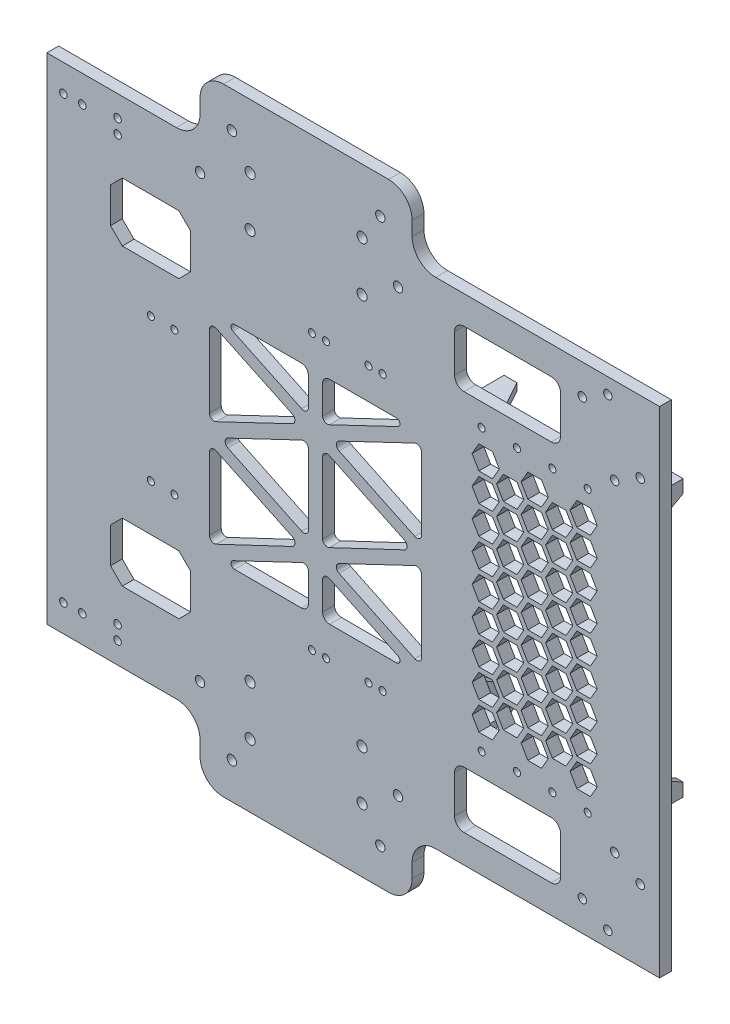
SolidWorks part; units mm, degrees
ref_plane "前视基准面" through (0, 0, 0) normal (0, 0, 1) x (1, 0, 0)
ref_plane "上视基准面" through (0, 0, 0) normal (0, 1, 0) x (1, 0, 0)
ref_plane "右视基准面" through (0, 0, 0) normal (1, 0, 0) x (0, 0, -1)
sketch "草图1" plane through (0, 0, 0) normal (0, 0, 1) x (1, 0, 0)
  line L2 (-130, 105) -> (-130, -105)
  line L3 (-130, -105) -> (-75, -105)
  line L4 (130, 95) -> (130, -95)
  line L5 (126.7518, 102.3765) -> (130, 105) construction
  line L9 (-65, -115) -> (-65, -121)
  line L10 (-55, -131) -> (15, -131)
  line L11 (25, -121) -> (25, -115)
  line L13 (35, -105) -> (120, -105)
  line L14 (126.7518, -102.3765) -> (130, -105) construction
  line L16 (-130, 0) -> (130, 0) construction
  line L17 (35, 105) -> (120, 105)
  line L18 (25, 121) -> (25, 115)
  line L19 (-55, 131) -> (15, 131)
  line L20 (-65, 115) -> (-65, 121)
  line L21 (-130, 105) -> (-75, 105)
  arc A3 (120, -105) -> (130, -95) centre (120, -95) ccw
  arc A8 (-65, -115) -> (-75, -105) centre (-75, -115) ccw
  arc A9 (25, -115) -> (35, -105) centre (35, -115) cw
  arc A10 (-55, -131) -> (-65, -121) centre (-55, -121) cw
  arc A11 (15, -131) -> (25, -121) centre (15, -121) ccw
  arc A12 (15, 131) -> (25, 121) centre (15, 121) cw
  arc A13 (-55, 131) -> (-65, 121) centre (-55, 121) ccw
  arc A14 (25, 115) -> (35, 105) centre (35, 115) ccw
  arc A15 (-65, 115) -> (-75, 105) centre (-75, 115) cw
  arc A16 (120, 105) -> (130, 95) centre (120, 95) cw
  point P0 (0, 0)
  point P7 (0, 0)
  point P10 (0, 0)
  point P11 (-130, -104.6435)
  point P34 (0, 0)
  point P36 (0, 0)
  point P40 (25, -105)
  point P45 (25, 105)
  point P47 (0, 0)
  dimension "D3" = 65
  dimension "D4" = 10
  dimension "D5" = 105
  dimension "D7" = 10
  dimension "D8" = 10
  dimension "D10" = 10
  dimension "D12" = 10
  dimension "D13" = 105
  dimension "D18" = 90
  dimension "D19" = 6
extrude "凸台-拉伸1" add sketch "草图1" along normal blind 5
sketch "草图4" plane through (0, 0, 0) normal (0, 0, -1) x (-1, 0, 0)
  line L0 (-39, -47.5) -> (-39, -58.5)
  line L1 (-39, -58.5) -> (-50, -58.5)
  line L2 (-50, -58.5) -> (-50, -55.5)
  line L3 (-50, -55.5) -> (-42, -55.5)
  line L4 (-42, -55.5) -> (-42, -47.5)
  line L5 (-42, -47.5) -> (-39, -47.5)
  line L6 (-130, 0) -> (-25.5592, 0) construction
  line L7 (-130, -95) -> (-130, 95) construction
  line L10 (-130, -95) -> (-130, 95) construction
  dimension "D1" = 11
  dimension "D2" = 11
  dimension "D3" = 3
  dimension "D4" = 3
  dimension "D5" = 80
  dimension "D7" = 55.5
extrude "凸台-拉伸2" add sketch "草图4" along normal blind 20
sketch "草图5" plane through (0, -58.5, 0) normal (0, -1, 0) x (1, 0, 0)
  line L0 (50, -10) -> (44.5, -20)
  line L1 (50, -20) -> (50, 0) construction
  line L2 (50, -20) -> (39, -20) construction
  line L3 (44.5, -20) -> (50, -20)
  line L4 (50, -20) -> (50, -10)
  dimension "D1" = 10
  dimension "D2" = 5.5
extrude "切除-拉伸3" cut sketch "草图5" against normal blind 10
sketch "草图6" plane through (39, 0, 0) normal (-1, 0, 0) x (0, 0, 1)
  line L0 (-20, -53) -> (-10, -47.5)
  line L1 (-20, -58.5) -> (-20, -47.5) construction
  line L2 (-20, -47.5) -> (0, -47.5) construction
  line L3 (-10, -47.5) -> (-20, -47.5)
  line L4 (-20, -47.5) -> (-20, -53)
  dimension "D1" = 10
  dimension "D2" = 5.5
extrude "切除-拉伸4" cut sketch "草图6" against normal blind 10
ref_plane "基准面2" through (77, 0, 0) normal (1, 0, 0) x (0, 0, -1)
mirror "镜向1" about plane through (77, 0, 0) normal (1, 0, 0) of "凸台-拉伸2", "切除-拉伸4", "切除-拉伸3"
mirror "镜向2" about plane through (0, 0, 0) normal (0, 1, 0) of "镜向1"
sketch "草图7" plane through (0, 0, 0) normal (0, 0, -1) x (-1, 0, 0)
  line L4 (-112, -55.5) -> (-104, -55.5) construction
  line L5 (-112, 47.5) -> (-112, 55.5) construction
  line L6 (-112, 55.5) -> (-104, 55.5) construction
  line L7 (-92.013, 36) -> (-94.8997, 41)
  line L8 (-94.8997, 41) -> (-100.6732, 41)
  line L9 (-100.6732, 41) -> (-103.56, 36)
  line L10 (-103.56, 36) -> (-100.6732, 31)
  line L11 (-100.6732, 31) -> (-94.8997, 31)
  line L12 (-94.8997, 31) -> (-92.013, 36)
  line L13 (-77.0019, 36) -> (-97.7865, 36) construction
  line L14 (-74.1151, 31) -> (-71.2284, 36)
  line L15 (-71.2284, 36) -> (-74.1151, 41)
  line L16 (-74.1151, 41) -> (-79.8886, 41)
  line L17 (-79.8886, 41) -> (-82.7754, 36)
  line L18 (-82.7754, 36) -> (-79.8886, 31)
  line L19 (-79.8886, 31) -> (-74.1151, 31)
  line L20 (-92.013, 24) -> (-94.8997, 29)
  line L21 (-93.1677, 30) -> (-90.2809, 25)
  line L22 (-90.2809, 25) -> (-84.5074, 25)
  line L23 (-84.5074, 25) -> (-81.6207, 30)
  line L24 (-81.6207, 30) -> (-84.5074, 35)
  line L25 (-84.5074, 35) -> (-90.2809, 35)
  line L26 (-90.2809, 35) -> (-93.1677, 30)
  line L27 (-84.5074, 37) -> (-81.6207, 42)
  line L28 (-81.6207, 42) -> (-84.5074, 47)
  line L29 (-84.5074, 47) -> (-90.2809, 47)
  line L30 (-90.2809, 47) -> (-93.1677, 42)
  line L31 (-93.1677, 42) -> (-90.2809, 37)
  line L32 (-90.2809, 37) -> (-84.5074, 37)
  line L33 (-79.8886, 43) -> (-74.1151, 43)
  line L34 (-74.1151, 43) -> (-71.2284, 48)
  line L35 (-71.2284, 48) -> (-74.1151, 53)
  line L36 (-74.1151, 53) -> (-79.8886, 53)
  line L37 (-79.8886, 53) -> (-82.7754, 48)
  line L38 (-82.7754, 48) -> (-79.8886, 43)
  line L39 (-94.8997, 43) -> (-92.013, 48)
  line L40 (-92.013, 48) -> (-94.8997, 53)
  line L41 (-94.8997, 53) -> (-100.6732, 53)
  line L42 (-100.6732, 53) -> (-103.56, 48)
  line L43 (-103.56, 48) -> (-100.6732, 43)
  line L44 (-100.6732, 43) -> (-94.8997, 43)
  line L45 (-72.3831, 42) -> (-69.4963, 37)
  line L46 (-69.4963, 37) -> (-63.7228, 37)
  line L47 (-63.7228, 37) -> (-60.8361, 42)
  line L48 (-60.8361, 42) -> (-63.7228, 47)
  line L49 (-63.7228, 47) -> (-69.4963, 47)
  line L50 (-69.4963, 47) -> (-72.3831, 42)
  line L51 (-94.8997, 29) -> (-100.6732, 29)
  line L52 (-100.6732, 29) -> (-103.56, 24)
  line L53 (-103.56, 24) -> (-100.6732, 19)
  line L54 (-100.6732, 19) -> (-94.8997, 19)
  line L55 (-94.8997, 19) -> (-92.013, 24)
  line L56 (-93.1677, 18) -> (-90.2809, 13)
  line L57 (-90.2809, 13) -> (-84.5074, 13)
  line L58 (-84.5074, 13) -> (-81.6207, 18)
  line L59 (-81.6207, 18) -> (-84.5074, 23)
  line L60 (-84.5074, 23) -> (-90.2809, 23)
  line L61 (-90.2809, 23) -> (-93.1677, 18)
  line L62 (-74.1151, 19) -> (-71.2284, 24)
  line L63 (-71.2284, 24) -> (-74.1151, 29)
  line L64 (-74.1151, 29) -> (-79.8886, 29)
  line L65 (-79.8886, 29) -> (-82.7754, 24)
  line L66 (-82.7754, 24) -> (-79.8886, 19)
  line L67 (-79.8886, 19) -> (-74.1151, 19)
  line L68 (-72.3831, 30) -> (-69.4963, 25)
  line L69 (-69.4963, 25) -> (-63.7228, 25)
  line L70 (-63.7228, 25) -> (-60.8361, 30)
  line L71 (-60.8361, 30) -> (-63.7228, 35)
  line L72 (-63.7228, 35) -> (-69.4963, 35)
  line L73 (-69.4963, 35) -> (-72.3831, 30)
  line L74 (-92.013, 12) -> (-94.8997, 17)
  line L75 (-94.8997, 17) -> (-100.6732, 17)
  line L76 (-100.6732, 17) -> (-103.56, 12)
  line L77 (-103.56, 12) -> (-100.6732, 7)
  line L78 (-100.6732, 7) -> (-94.8997, 7)
  line L79 (-94.8997, 7) -> (-92.013, 12)
  line L80 (-93.1677, 6) -> (-90.2809, 1)
  line L81 (-90.2809, 1) -> (-84.5074, 1)
  line L82 (-84.5074, 1) -> (-81.6207, 6)
  line L83 (-81.6207, 6) -> (-84.5074, 11)
  line L84 (-84.5074, 11) -> (-90.2809, 11)
  line L85 (-90.2809, 11) -> (-93.1677, 6)
  line L86 (-74.1151, 7) -> (-71.2284, 12)
  line L87 (-71.2284, 12) -> (-74.1151, 17)
  line L88 (-74.1151, 17) -> (-79.8886, 17)
  line L89 (-79.8886, 17) -> (-82.7754, 12)
  line L90 (-82.7754, 12) -> (-79.8886, 7)
  line L91 (-79.8886, 7) -> (-74.1151, 7)
  line L92 (-72.3831, 18) -> (-69.4963, 13)
  line L93 (-69.4963, 13) -> (-63.7228, 13)
  line L94 (-63.7228, 13) -> (-60.8361, 18)
  line L95 (-60.8361, 18) -> (-63.7228, 23)
  line L96 (-63.7228, 23) -> (-69.4963, 23)
  line L97 (-69.4963, 23) -> (-72.3831, 18)
  line L98 (-92.013, 0) -> (-94.8997, 5)
  line L99 (-94.8997, 5) -> (-100.6732, 5)
  line L100 (-100.6732, 5) -> (-103.56, 0)
  line L101 (-103.56, 0) -> (-100.6732, -5)
  line L102 (-100.6732, -5) -> (-94.8997, -5)
  line L103 (-94.8997, -5) -> (-92.013, 0)
  line L104 (-93.1677, -6) -> (-90.2809, -11)
  line L105 (-90.2809, -11) -> (-84.5074, -11)
  line L106 (-84.5074, -11) -> (-81.6207, -6)
  line L107 (-81.6207, -6) -> (-84.5074, -1)
  line L108 (-84.5074, -1) -> (-90.2809, -1)
  line L109 (-90.2809, -1) -> (-93.1677, -6)
  line L110 (-74.1151, -5) -> (-71.2284, 0)
  line L111 (-71.2284, 0) -> (-74.1151, 5)
  line L112 (-74.1151, 5) -> (-79.8886, 5)
  line L113 (-79.8886, 5) -> (-82.7754, 0)
  line L114 (-82.7754, 0) -> (-79.8886, -5)
  line L115 (-79.8886, -5) -> (-74.1151, -5)
  line L116 (-72.3831, 6) -> (-69.4963, 1)
  line L117 (-69.4963, 1) -> (-63.7228, 1)
  line L118 (-63.7228, 1) -> (-60.8361, 6)
  line L119 (-60.8361, 6) -> (-63.7228, 11)
  line L120 (-63.7228, 11) -> (-69.4963, 11)
  line L121 (-69.4963, 11) -> (-72.3831, 6)
  line L122 (-92.013, -12) -> (-94.8997, -7)
  line L123 (-94.8997, -7) -> (-100.6732, -7)
  line L124 (-100.6732, -7) -> (-103.56, -12)
  line L125 (-103.56, -12) -> (-100.6732, -17)
  line L126 (-100.6732, -17) -> (-94.8997, -17)
  line L127 (-94.8997, -17) -> (-92.013, -12)
  line L128 (-93.1677, -18) -> (-90.2809, -23)
  line L129 (-90.2809, -23) -> (-84.5074, -23)
  line L130 (-84.5074, -23) -> (-81.6207, -18)
  line L131 (-81.6207, -18) -> (-84.5074, -13)
  line L132 (-84.5074, -13) -> (-90.2809, -13)
  line L133 (-90.2809, -13) -> (-93.1677, -18)
  line L134 (-74.1151, -17) -> (-71.2284, -12)
  line L135 (-71.2284, -12) -> (-74.1151, -7)
  line L136 (-74.1151, -7) -> (-79.8886, -7)
  line L137 (-79.8886, -7) -> (-82.7754, -12)
  line L138 (-82.7754, -12) -> (-79.8886, -17)
  line L139 (-79.8886, -17) -> (-74.1151, -17)
  line L140 (-72.3831, -6) -> (-69.4963, -11)
  line L141 (-69.4963, -11) -> (-63.7228, -11)
  line L142 (-63.7228, -11) -> (-60.8361, -6)
  line L143 (-60.8361, -6) -> (-63.7228, -1)
  line L144 (-63.7228, -1) -> (-69.4963, -1)
  line L145 (-69.4963, -1) -> (-72.3831, -6)
  line L146 (-92.013, -24) -> (-94.8997, -19)
  line L147 (-94.8997, -19) -> (-100.6732, -19)
  line L148 (-100.6732, -19) -> (-103.56, -24)
  line L149 (-103.56, -24) -> (-100.6732, -29)
  line L150 (-100.6732, -29) -> (-94.8997, -29)
  line L151 (-94.8997, -29) -> (-92.013, -24)
  line L152 (-93.1677, -30) -> (-90.2809, -35)
  line L153 (-90.2809, -35) -> (-84.5074, -35)
  line L154 (-84.5074, -35) -> (-81.6207, -30)
  line L155 (-81.6207, -30) -> (-84.5074, -25)
  line L156 (-84.5074, -25) -> (-90.2809, -25)
  line L157 (-90.2809, -25) -> (-93.1677, -30)
  line L158 (-74.1151, -29) -> (-71.2284, -24)
  line L159 (-71.2284, -24) -> (-74.1151, -19)
  line L160 (-74.1151, -19) -> (-79.8886, -19)
  line L161 (-79.8886, -19) -> (-82.7754, -24)
  line L162 (-82.7754, -24) -> (-79.8886, -29)
  line L163 (-79.8886, -29) -> (-74.1151, -29)
  line L164 (-72.3831, -18) -> (-69.4963, -23)
  line L165 (-69.4963, -23) -> (-63.7228, -23)
  line L166 (-63.7228, -23) -> (-60.8361, -18)
  line L167 (-60.8361, -18) -> (-63.7228, -13)
  line L168 (-63.7228, -13) -> (-69.4963, -13)
  line L169 (-69.4963, -13) -> (-72.3831, -18)
  line L170 (-92.013, -36) -> (-94.8997, -31)
  line L171 (-94.8997, -31) -> (-100.6732, -31)
  line L172 (-100.6732, -31) -> (-103.56, -36)
  line L173 (-103.56, -36) -> (-100.6732, -41)
  line L174 (-100.6732, -41) -> (-94.8997, -41)
  line L175 (-94.8997, -41) -> (-92.013, -36)
  line L176 (-93.1677, -42) -> (-90.2809, -47)
  line L177 (-90.2809, -47) -> (-84.5074, -47)
  line L178 (-84.5074, -47) -> (-81.6207, -42)
  line L179 (-81.6207, -42) -> (-84.5074, -37)
  line L180 (-84.5074, -37) -> (-90.2809, -37)
  line L181 (-90.2809, -37) -> (-93.1677, -42)
  line L182 (-74.1151, -41) -> (-71.2284, -36)
  line L183 (-71.2284, -36) -> (-74.1151, -31)
  line L184 (-74.1151, -31) -> (-79.8886, -31)
  line L185 (-79.8886, -31) -> (-82.7754, -36)
  line L186 (-82.7754, -36) -> (-79.8886, -41)
  line L187 (-79.8886, -41) -> (-74.1151, -41)
  line L188 (-72.3831, -30) -> (-69.4963, -35)
  line L189 (-69.4963, -35) -> (-63.7228, -35)
  line L190 (-63.7228, -35) -> (-60.8361, -30)
  line L191 (-60.8361, -30) -> (-63.7228, -25)
  line L192 (-63.7228, -25) -> (-69.4963, -25)
  line L193 (-69.4963, -25) -> (-72.3831, -30)
  line L194 (-92.013, -48) -> (-94.8997, -43)
  line L195 (-94.8997, -43) -> (-100.6732, -43)
  line L196 (-100.6732, -43) -> (-103.56, -48)
  line L197 (-103.56, -48) -> (-100.6732, -53)
  line L198 (-100.6732, -53) -> (-94.8997, -53)
  line L199 (-94.8997, -53) -> (-92.013, -48)
  line L206 (-74.1151, -53) -> (-71.2284, -48)
  line L207 (-71.2284, -48) -> (-74.1151, -43)
  line L208 (-74.1151, -43) -> (-79.8886, -43)
  line L209 (-79.8886, -43) -> (-82.7754, -48)
  line L210 (-82.7754, -48) -> (-79.8886, -53)
  line L211 (-79.8886, -53) -> (-74.1151, -53)
  line L212 (-72.3831, -42) -> (-69.4963, -47)
  line L213 (-69.4963, -47) -> (-63.7228, -47)
  line L214 (-63.7228, -47) -> (-60.8361, -42)
  line L215 (-60.8361, -42) -> (-63.7228, -37)
  line L216 (-63.7228, -37) -> (-69.4963, -37)
  line L217 (-69.4963, -37) -> (-72.3831, -42)
  line L218 (-61.9908, 36) -> (-59.104, 31)
  line L219 (-61.9908, 48) -> (-59.104, 43)
  line L220 (-59.104, 43) -> (-53.3305, 43)
  line L221 (-53.3305, 43) -> (-50.4438, 48)
  line L222 (-50.4438, 48) -> (-53.3305, 53)
  line L223 (-53.3305, 53) -> (-59.104, 53)
  line L224 (-59.104, 53) -> (-61.9908, 48)
  line L225 (-59.104, 31) -> (-53.3305, 31)
  line L226 (-53.3305, 31) -> (-50.4438, 36)
  line L227 (-50.4438, 36) -> (-53.3305, 41)
  line L228 (-53.3305, 41) -> (-59.104, 41)
  line L229 (-59.104, 41) -> (-61.9908, 36)
  line L230 (-61.9908, 24) -> (-59.104, 19)
  line L231 (-59.104, 19) -> (-53.3305, 19)
  line L232 (-53.3305, 19) -> (-50.4438, 24)
  line L233 (-50.4438, 24) -> (-53.3305, 29)
  line L234 (-53.3305, 29) -> (-59.104, 29)
  line L235 (-59.104, 29) -> (-61.9908, 24)
  line L236 (-61.9908, 12) -> (-59.104, 7)
  line L237 (-59.104, 7) -> (-53.3305, 7)
  line L238 (-53.3305, 7) -> (-50.4438, 12)
  line L239 (-50.4438, 12) -> (-53.3305, 17)
  line L240 (-53.3305, 17) -> (-59.104, 17)
  line L241 (-59.104, 17) -> (-61.9908, 12)
  line L242 (-61.9908, 0) -> (-59.104, -5)
  line L243 (-59.104, -5) -> (-53.3305, -5)
  line L244 (-53.3305, -5) -> (-50.4438, 0)
  line L245 (-50.4438, 0) -> (-53.3305, 5)
  line L246 (-53.3305, 5) -> (-59.104, 5)
  line L247 (-59.104, 5) -> (-61.9908, 0)
  line L248 (-61.9908, -12) -> (-59.104, -17)
  line L249 (-59.104, -17) -> (-53.3305, -17)
  line L250 (-53.3305, -17) -> (-50.4438, -12)
  line L251 (-50.4438, -12) -> (-53.3305, -7)
  line L252 (-53.3305, -7) -> (-59.104, -7)
  line L253 (-59.104, -7) -> (-61.9908, -12)
  line L254 (-61.9908, -24) -> (-59.104, -29)
  line L255 (-59.104, -29) -> (-53.3305, -29)
  line L256 (-53.3305, -29) -> (-50.4438, -24)
  line L257 (-50.4438, -24) -> (-53.3305, -19)
  line L258 (-53.3305, -19) -> (-59.104, -19)
  line L259 (-59.104, -19) -> (-61.9908, -24)
  line L260 (-61.9908, -36) -> (-59.104, -41)
  line L261 (-59.104, -41) -> (-53.3305, -41)
  line L262 (-53.3305, -41) -> (-50.4438, -36)
  line L263 (-50.4438, -36) -> (-53.3305, -31)
  line L264 (-53.3305, -31) -> (-59.104, -31)
  line L265 (-59.104, -31) -> (-61.9908, -36)
  line L266 (-61.9908, -48) -> (-59.104, -53)
  line L267 (-59.104, -53) -> (-53.3305, -53)
  line L268 (-53.3305, -53) -> (-50.4438, -48)
  line L269 (-50.4438, -48) -> (-53.3305, -43)
  line L270 (-53.3305, -43) -> (-59.104, -43)
  line L271 (-59.104, -43) -> (-61.9908, -48)
  line L272 (-93.1677, -54) -> (-90.2809, -59) [skipped]
  line L273 (-90.2809, -59) -> (-84.5074, -59) [skipped]
  line L274 (-84.5074, -59) -> (-81.6207, -54) [skipped]
  line L275 (-81.6207, -54) -> (-84.5074, -49) [skipped]
  line L276 (-84.5074, -49) -> (-90.2809, -49) [skipped]
  line L277 (-90.2809, -49) -> (-93.1677, -54) [skipped]
  circle A0 centre (-97.7865, 36) radius 5 construction
  circle A1 centre (-77.0019, 36) radius 5 construction
  circle A2 centre (-87.3942, 30) radius 5 construction
  circle A3 centre (-87.3942, 42) radius 5 construction
  circle A4 centre (-77.0019, 48) radius 5 construction
  circle A5 centre (-97.7865, 48) radius 5 construction
  circle A6 centre (-66.6096, 42) radius 5 construction
  circle A7 centre (-56.2173, 48) radius 5 construction
  point P4 (-87.3942, 37)
  dimension "D1" = 2
  dimension "D3" = 10
  dimension "D4" = 10
  dimension "D5" = 2
  dimension "D7" = 10
  dimension "D11" = 10
  dimension "D14" = 10
  dimension "D15" = 10
  dimension "D20" = 10
  dimension "D2" = 2
  dimension "D6" = 2
  dimension "D8" = 2
  dimension "D9" = 2
  dimension "D10" = 2
  dimension "D12" = 2
  dimension "D13" = 2
  dimension "D16" = 2
  dimension "D17" = 2
  dimension "D19" = 2
  dimension "D21" = 9
  dimension "D22" = 2.5
  dimension "D23" = 2.5
  dimension "D24" = 8.44
  dimension "D18" = 8
extrude "切除-拉伸5" cut sketch "草图7" against normal blind 5
sketch "草图8" plane through (0, 0, 0) normal (0, 0, -1) x (-1, 0, 0)
  line L0 (-75.3677, 120) -> (-75.3677, -120)
  line L1 (-100.0285, 77.2863) -> (-100.0285, -77.2863)
  line L2 (-100.0285, 77.2863) -> (-75.3677, 120)
  line L3 (-100.0285, -77.2863) -> (-75.3677, -120)
  line L4 (-37.1297, 0) -> (-146.8562, 0) construction
  dimension "D1" = 30
  dimension "D2" = 30
  dimension "D3" = 120
  dimension "D4" = 120
sketch "草图9" plane through (0, 0, 0) normal (0, 0, -1) x (-1, 0, 0)
  line L0 (148.8518, 0) -> (-37.1297, 0) construction
  line L1 (-29, 41) -> (-29, 4)
  line L2 (-25, -45) -> (13, -45)
  line L3 (61, -41) -> (61, -4)
  line L4 (57, 45) -> (19, 45)
  line L14 (-29, 41) -> (9.8049, 22.5)
  line L15 (57, 0) -> (19, -18.1163)
  line L16 (130, 105) -> (130, -105) construction
  line L17 (63, 93) -> (118, 93)
  line L18 (63, 93) -> (63, 66)
  line L19 (63, 66) -> (118, 66)
  line L20 (118, 93) -> (118, 66)
  line L21 (75, 105) -> (130, 105) construction
  line L22 (63, -66) -> (118, -66)
  line L23 (118, -93) -> (118, -66)
  line L24 (63, -93) -> (118, -93)
  line L25 (63, -93) -> (63, -66)
  line L26 (-120, 105) -> (-35, 105) construction
  line L27 (-43, 93) -> (-88, 93)
  line L28 (-43, 93) -> (-43, 69)
  line L29 (-43, 69) -> (-88, 69)
  line L30 (-88, 93) -> (-88, 69)
  line L31 (-130, -95) -> (-130, 95) construction
  line L32 (-43, -69) -> (-88, -69)
  line L33 (-88, -93) -> (-88, -69)
  line L34 (-43, -93) -> (-88, -93)
  line L35 (-43, -93) -> (-43, -69)
  line L36 (-25, 45) -> (13, 26.8837)
  line L37 (-25, -45) -> (13, -26.8837)
  line L38 (61, 41) -> (22.0746, 22.5575)
  line L39 (-25.5359, 0) -> (13, -18.258)
  line L40 (57, 45) -> (19, 26.8837)
  line L41 (57, -45) -> (19, -26.8837)
  line L42 (16, 61.4977) -> (16, -60.5731) construction
  line L43 (13, 45) -> (13, 26.8837)
  line L44 (19, 45) -> (19, 26.8837)
  line L45 (13, 18.258) -> (13, -18.258)
  line L46 (9.8049, 22.5) -> (-29, 4)
  line L47 (19, 18.1163) -> (57, 0)
  line L48 (22.0746, 22.5575) -> (61, 4)
  line L49 (13, 18.258) -> (-25.5359, 0)
  line L50 (19, 18.1163) -> (19, -18.1163)
  line L51 (22.0746, -22.5575) -> (61, -41)
  line L52 (9.8049, -22.5) -> (-29, -41)
  line L53 (9.8049, -22.5) -> (-29, -4)
  line L54 (22.0746, -22.5575) -> (61, -4)
  line L55 (13, -26.8837) -> (13, -45)
  line L56 (19, -26.8837) -> (19, -45)
  line L57 (13, 45) -> (-25, 45)
  line L58 (-29, -4) -> (-29, -41)
  line L59 (19, -45) -> (57, -45)
  line L60 (61, 4) -> (61, 41)
  line L61 (-44, 41) -> (-44, -37.8122) construction
  dimension "D1" = 45
  dimension "D2" = 45
  dimension "D3" = 15
  dimension "D4" = 90
  dimension "D5" = 1
  dimension "D7" = 12
  dimension "D8" = 12
  dimension "D9" = 27
  dimension "D10" = 55
  dimension "D11" = 12
  dimension "D12" = 45
  dimension "D13" = 42
  dimension "D14" = 24
  dimension "D21" = 4
  dimension "D22" = 4
  dimension "D23" = 4
  dimension "D24" = 4
  dimension "D26" = 4
  dimension "D27" = 3
  dimension "D28" = 45
extrude "切除-拉伸6" cut sketch "草图9" against normal blind 5 contours L27 L30 L29 L28 | L34 L35 L32 L33 | L4 L44 L40 | L48 L60 L38 | L47 L50 L15 | L54 L51 L3 | L56 L59 L41 | L55 L37 L2 | L53 L58 L52 | L45 L49 L39 | L46 L14 L1 | L43 L57 L36 | L57 L36 L43 region at (16.065, 22.5, 0) region at (-0.3333, -38.9612, 0) region at (-48.0249, -22.5192, 0) region at (-31.6667, 38.9612, 0) region at (-31.6667, 0, 0) region at (65.5, 81, 0) region at (65.5, -81, 0) region at (-0.3333, 38.9612, 0) region at (-48.0249, 22.5192, 0) region at (-0.1547, 0, 0) region at (-31.6667, -38.9612, 0) region at (16.065, -22.5, 0)
fillet "圆角1" radius 4 8 edges at (43, -93, 2.5) (88, -69, 2.5) (43, -69, 2.5) (88, -93, 2.5) (88, 69, 2.5) (43, 69, 2.5) (43, 93, 2.5) (88, 93, 2.5)
fillet "圆角2" radius 1.5 4 edges at (25, -45, 2.5) (-57, -45, 2.5) (25, 45, 2.5) (-57, 45, 2.5)
fillet "圆角3" radius 2 22 edges at (29, -4, 2.5) (29, 4, 2.5) (-13, -18.258, 2.5) (-61, -41, 2.5) (-61, 4, 2.5) (-13, -26.8837, 2.5) (-13, 18.258, 2.5) (-61, -4, 2.5) (-22.0746, -22.5575, 2.5) (25.5359, 0, 2.5) (-22.0746, 22.5575, 2.5) (-61, 41, 2.5) (-19, 26.8837, 2.5) (-19, -26.8837, 2.5) (-19, -18.1163, 2.5) (29, -41, 2.5) (29, 41, 2.5) (-57, 0, 2.5) (-9.8049, -22.5, 2.5) (-13, 26.8837, 2.5) (-9.8049, 22.5, 2.5) (-19, 18.1163, 2.5)
fillet "圆角4" radius 3 4 edges at (-13, -45, 2.5) (-13, 45, 2.5) (-19, -45, 2.5) (-19, 45, 2.5)
sketch "草图12" plane through (0, 0, 0) normal (0, 0, -1) x (-1, 0, 0)
  line L1 (-120, 105) -> (-130, 105)
  line L2 (-120, 105) -> (-120, -105)
  line L3 (-120, -105) -> (-130, -105)
  line L4 (-130, 105) -> (-130, -105)
extrude "凸台-拉伸3" add sketch "草图12" against normal up to surface (5 mm away) up to face at (65.5, 81, 5)
hole_wizard "M3 六角头螺栓的柱形沉头孔1" positions "草图16" profile "草图17" counterbore size "M3" standard "GB" end condition through all
sketch "草图16" plane through (-124.3639, -131.0101, -4.2) normal (0, 0, -1) x (0, 1, 0)
  point P0 (221.0101, 24.3639)
  point P3 (227.0101, 24.3639)
sketch "草图17" plane through (-100, 90, -4.2) normal (1, 0, 0) x (0, 1, 0)
  line L0 (0, 0) -> (0, 9.2)
  line L1 (0, 9.2) -> (1.6, 9.2)
  line L2 (1.6, 9.2) -> (1.6, 1.6)
  line L3 (1.6, 1.6) -> (2.95, 1.6)
  line L4 (2.95, 1.6) -> (2.95, 0)
  line L5 (2.95, 0) -> (0, 0)
  line L6 (0, -6.35) -> (0, 107.95) construction
  dimension "通孔孔直径" = 3.2
  dimension "通孔孔深度" = 9.2
  dimension "柱形沉头孔直径" = 5.9
  dimension "柱形沉头孔深度" = 1.6
sketch "草图10" plane through (0, 0, 0) normal (0, 0, -1) x (-1, 0, 0)
  line L0 (-37.1297, 0) -> (-146.8562, 0) construction
  line L1 (-37.1297, 0) -> (-146.8562, 0) construction
  circle A0 centre (-121.782, 74.6081) radius 1.8 construction
  circle A1 centre (-110.9567, 68.3581) radius 1.8 construction
  circle A2 centre (-108.032, 98.4238) radius 1.8 construction
  circle A3 centre (-97.2067, 92.1738) radius 1.8 construction
  circle A4 centre (-3.75, 104) radius 2.15 construction
  circle A5 centre (-3.75, 104) radius 2.15
  circle A6 centre (-3.75, -104) radius 2.15
  circle A7 centre (115, 93.5) radius 1.6 construction
  circle A8 centre (123, 93.5) radius 1.6 construction
  circle A9 centre (115, 93.5) radius 1.6
  circle A10 centre (123, 93.5) radius 1.6
  circle A11 centre (123, -93.5) radius 1.6
  circle A12 centre (115, -93.5) radius 1.6
  circle A13 centre (100, 96) radius 1.6 construction
  circle A14 centre (100, 90) radius 1.6 construction
  circle A15 centre (-121.782, 74.6081) radius 1.8
  circle A16 centre (-110.9567, 68.3581) radius 1.8
  circle A17 centre (-108.032, 98.4238) radius 1.8
  circle A18 centre (-97.2067, 92.1738) radius 1.8
  circle A41 centre (-97.2067, -92.1738) radius 1.8
  circle A42 centre (-108.032, -98.4238) radius 1.8
  circle A43 centre (-110.9567, -68.3581) radius 1.8
  circle A44 centre (-121.782, -74.6081) radius 1.8
  circle A45 centre (-99.5, 59.5) radius 1.5 construction
  circle A46 centre (-84.5, 59.5) radius 1.5 construction
  circle A47 centre (-69.5, 59.5) radius 1.5 construction
  circle A48 centre (-54.5, 59.5) radius 1.5 construction
  circle A49 centre (-12.4571, 58.25) radius 1.5 construction
  circle A50 centre (-6.4571, 58.25) radius 1.5 construction
  circle A51 centre (11.5429, 58.25) radius 1.5 construction
  circle A52 centre (17.5429, 58.25) radius 1.5 construction
  circle A53 centre (-99.5, 59.5) radius 1.5
  circle A54 centre (-84.5, 59.5) radius 1.5
  circle A55 centre (-69.5, 59.5) radius 1.5
  circle A56 centre (-54.5, 59.5) radius 1.5
  circle A57 centre (-12.4571, 58.25) radius 1.5
  circle A58 centre (-6.4571, 58.25) radius 1.5
  circle A59 centre (11.5429, 58.25) radius 1.5
  circle A60 centre (17.5429, 58.25) radius 1.5
  circle A61 centre (17.5429, -58.25) radius 1.5
  circle A62 centre (11.5429, -58.25) radius 1.5
  circle A63 centre (-6.4571, -58.25) radius 1.5
  circle A64 centre (-12.4571, -58.25) radius 1.5
  circle A65 centre (-54.5, -59.5) radius 1.5
  circle A66 centre (-69.5, -59.5) radius 1.5
  circle A67 centre (-84.5, -59.5) radius 1.5
  circle A68 centre (-99.5, -59.5) radius 1.5
  circle A69 centre (100, 96) radius 1.6
  circle A70 centre (100, 90) radius 1.6
  circle A71 centre (100, -90) radius 1.6
  circle A72 centre (100, -96) radius 1.6
  circle A89 centre (75.897, 30.3) radius 1.5 construction
  circle A90 centre (85.897, 30.3) radius 1.5 construction
  circle A91 centre (75.897, 30.3) radius 1.5
  circle A92 centre (85.897, 30.3) radius 1.5
  circle A93 centre (85.897, -30.3) radius 1.5
  circle A94 centre (75.897, -30.3) radius 1.5
  circle A95 centre (43.75, 83) radius 2.15 construction
  circle A96 centre (43.75, 104) radius 2.15 construction
  circle A97 centre (-3.75, 83) radius 2.15 construction
  circle A99 centre (43.75, 83) radius 2.15
  circle A100 centre (43.75, 104) radius 2.15
  circle A101 centre (-3.75, 83) radius 2.15
  circle A104 centre (-3.75, -83) radius 2.15
  circle A105 centre (43.75, -104) radius 2.15
  circle A106 centre (43.75, -83) radius 2.15
extrude "切除-拉伸7" cut sketch "草图10" against normal through all
sketch "草图11" plane through (0, 0, 0) normal (0, 0, -1) x (-1, 0, 0)
  line L0 (130, 105) -> (130, -105) construction
  line L1 (74, -75) -> (98, -75)
  line L2 (69, -70) -> (69, -55)
  line L3 (74, -50) -> (98, -50)
  line L4 (103, -70) -> (103, -55)
  line L5 (130, 0) -> (108.529, 0) construction
  line L10 (69, -70) -> (74, -75)
  line L11 (69, -55) -> (74, -50)
  line L12 (98, -50) -> (103, -55)
  line L13 (98, -75) -> (103, -70)
  line L14 (98, 75) -> (103, 70)
  line L15 (98, 50) -> (103, 55)
  line L16 (69, 55) -> (74, 50)
  line L17 (69, 70) -> (74, 75)
  line L18 (103, 70) -> (103, 55)
  line L19 (74, 50) -> (98, 50)
  line L20 (69, 70) -> (69, 55)
  line L21 (74, 75) -> (98, 75)
  point P0 (69, -75)
  point P1 (103, -50)
  point P2 (69, -50)
  point P3 (103, -75)
  point P8 (103, 75)
  point P9 (69, 50)
  point P10 (103, 50)
  point P11 (69, 75)
  dimension "D1" = 34
  dimension "D2" = 25
  dimension "D3" = 27
  dimension "D4" = 50
extrude "切除-拉伸8" cut sketch "草图11" against normal through all
sketch "草图14" plane through (0, 0, 5) normal (0, 0, 1) x (1, 0, 0)
  line L0 (25, -121) -> (25, -115) construction
  line L1 (-55, -131) -> (15, -131) construction
  line L2 (-20, -131) -> (-20, 131) construction
  line L3 (15, 131) -> (-55, 131) construction
  line L4 (-20, 0) -> (-130, 0) construction
  line L5 (-130, 105) -> (-130, -105) construction
  circle A0 centre (11.5, -115.68) radius 2
  circle A1 centre (-51.5, -115.68) radius 2
  circle A2 centre (-51.5, 115.68) radius 2
  circle A3 centre (11.5, 115.68) radius 2
  dimension "D1" = 4
  dimension "D2" = 13.5
  dimension "D3" = 15.32
extrude "切除-拉伸9" cut sketch "草图14" against normal blind 10
sketch "草图15" plane through (0, 0, 0) normal (0, 0, -1) x (-1, 0, 0)
  line L0 (65, -93.5) -> (-19, -93.5) construction
  line L1 (130, 0) -> (-85.2757, 0) construction
  line L2 (130, 105) -> (130, -105) construction
  line L3 (-25, -121) -> (-25, -115) construction
  circle A0 centre (65, -93.5) radius 2
  circle A1 centre (-19, -93.5) radius 2
  circle A2 centre (65, 93.5) radius 2
  circle A3 centre (-19, 93.5) radius 2
  dimension "D1" = 4
  dimension "D3" = 6
  dimension "D2" = 84
extrude "切除-拉伸10" cut sketch "草图15" against normal through all
equation "\"45、\"=43.7672"
